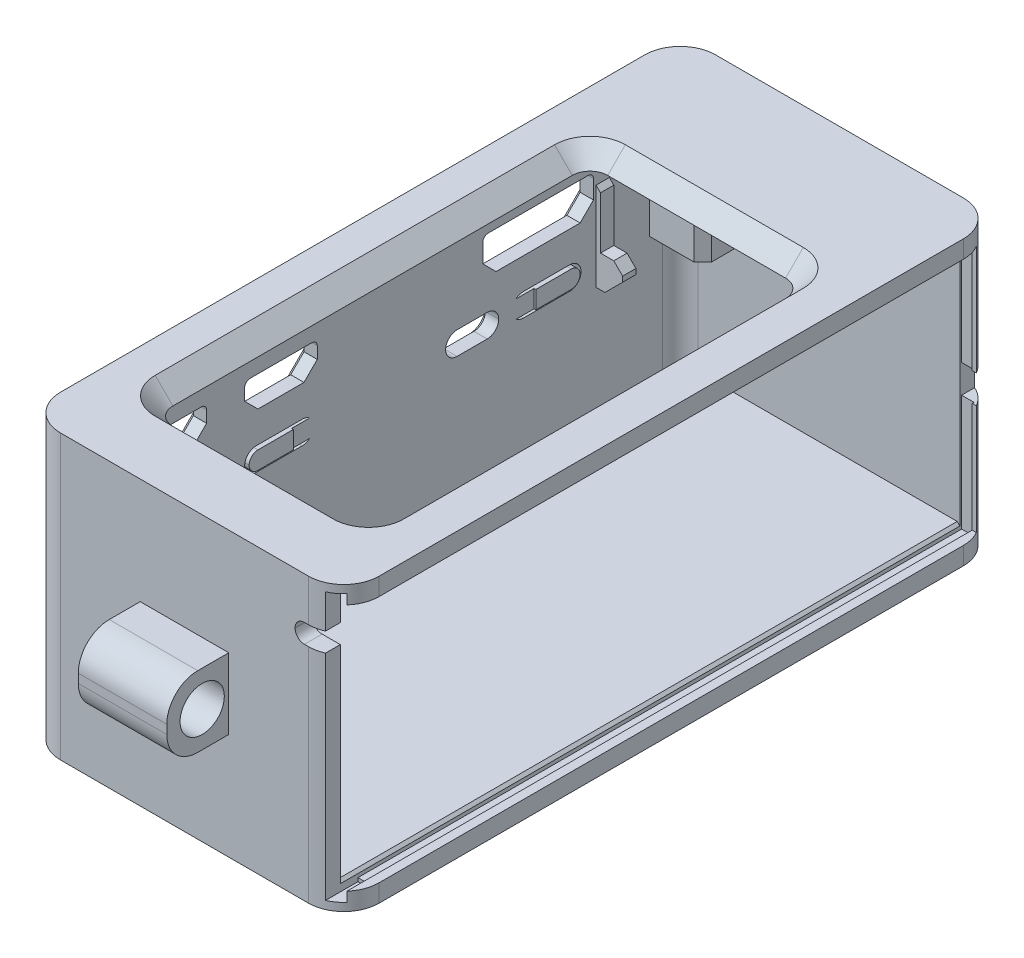
SolidWorks part; units mm, degrees
ref_plane "前视基准面" through (0, 0, 0) normal (0, 0, 1) x (1, 0, 0)
ref_plane "上视基准面" through (0, 0, 0) normal (0, 1, 0) x (1, 0, 0)
ref_plane "右视基准面" through (0, 0, 0) normal (1, 0, 0) x (0, 0, -1)
sketch "草图1" plane through (0, 0, 0) normal (1, 0, 0) x (0, 0, -1)
  line L1 (-54.0501, 29.0398) -> (19.9499, 29.0398)
  line L2 (-54.0501, 29.0398) -> (-54.0501, -2.9602)
  line L3 (-54.0501, -2.9602) -> (19.9499, -2.9602)
  line L4 (19.9499, 29.0398) -> (19.9499, -2.9602)
  dimension "D1" = 74
  dimension "D2" = 32
extrude "凸台-拉伸1" add sketch "草图1" along normal blind 36
sketch "草图2" plane through (36, 0, 0) normal (1, 0, 0) x (0, 0, -1)
  line L8 (17.9499, -0.9602) -> (17.9499, 27.0398)
  line L9 (-52.0501, -0.9602) -> (17.9499, -0.9602)
  line L10 (-52.0501, 27.0398) -> (-52.0501, -0.9602)
  line L11 (17.9499, 27.0398) -> (-52.0501, 27.0398)
  line L12 (17.9499, -0.9602) -> (17.9499, 27.0398)
  line L13 (-52.0501, -0.9602) -> (17.9499, -0.9602)
  line L14 (-52.0501, 27.0398) -> (-52.0501, -0.9602)
  line L15 (17.9499, 27.0398) -> (-52.0501, 27.0398)
  dimension "D1" = 2
extrude "切除-拉伸1" cut sketch "草图2" against normal blind 34
fillet "圆角1" radius 2 2 edges at (2, 13.0398, -17.9499) (2, 13.0398, 52.0501)
fillet "圆角2" radius 4 4 edges at (0, 13.0398, -19.9499) (0, 13.0398, 54.0501) (36, 13.0398, 54.0501) (36, 13.0398, -19.9499)
sketch "草图3" plane through (0, 29.0398, 0) normal (0, 1, 0) x (1, 0, 0)
  line L0 (32, 19.9499) -> (4, 19.9499) construction
  line L1 (29.8, 4.0599) -> (5.7, 4.0599)
  line L2 (29.8, 4.0599) -> (29.8, -45.0601)
  line L3 (29.8, -45.0601) -> (5.7, -45.0601)
  line L4 (5.7, 4.0599) -> (5.7, -45.0601)
  line L5 (36, 15.9499) -> (36, -50.0501) construction
  line L6 (32, -54.0501) -> (4, -54.0501) construction
  line L7 (0, 15.9499) -> (0, -50.0501) construction
  dimension "D1" = 15.89
  dimension "D2" = 6.2
  dimension "D3" = 8.99
  dimension "D4" = 5.7
extrude "切除-拉伸2" cut sketch "草图3" against normal blind 10
fillet "圆角3" radius 2 4 edges at (5.7, 28.0398, 45.0601) (29.8, 28.0398, 45.0601) (29.8, 28.0398, -4.0599) (5.7, 28.0398, -4.0599)
chamfer "倒角1" distance 2 angle 45 8 edges at (17.75, 29.0398, 45.0601) (29.2142, 29.0398, 44.4744) (6.2858, 29.0398, 44.4744) (29.8, 29.0398, 20.5001) (5.7, 29.0398, 20.5001) (29.2142, 29.0398, -3.4741) (6.2858, 29.0398, -3.4741) (17.75, 29.0398, -4.0599)
sketch "草图4" plane through (0, 0, 0) normal (-1, 0, 0) x (0, 0, 1)
  line L0 (-15.9499, 29.0398) -> (50.0501, 29.0398) construction
  line L1 (-8.1499, 22.4398) -> (4.3501, 22.4398)
  line L2 (-8.1499, 22.4398) -> (-8.1499, 18.2398)
  line L3 (-8.1499, 18.2398) -> (4.3501, 18.2398)
  line L4 (4.3501, 22.4398) -> (4.3501, 18.2398)
  line L5 (23.0501, 21.6812) -> (31.2501, 21.6812)
  line L6 (23.0501, 21.6812) -> (23.0501, 18.2398)
  line L7 (23.0501, 18.2398) -> (31.2501, 18.2398)
  line L8 (31.2501, 21.6812) -> (31.2501, 18.2398)
  line L9 (35.5501, 21.6398) -> (43.7501, 21.6398)
  line L10 (35.5501, 21.6398) -> (35.5501, 18.2398)
  line L11 (35.5501, 18.2398) -> (43.7501, 18.2398)
  line L12 (43.7501, 21.6398) -> (43.7501, 18.2398)
  line L13 (-6.7499, 14.7398) -> (1.0501, 14.7398)
  line L14 (-6.7499, 14.7398) -> (-6.7499, 12.1398)
  line L15 (-6.7499, 12.1398) -> (1.0501, 12.1398)
  line L16 (1.0501, 14.7398) -> (1.0501, 12.1398)
  line L17 (23.4501, 14.7398) -> (31.2501, 14.7398)
  line L18 (23.4501, 14.7398) -> (23.4501, 12.1398)
  line L19 (23.4501, 12.1398) -> (31.2501, 12.1398)
  line L20 (31.2501, 14.7398) -> (31.2501, 12.1398)
  line L21 (33.8696, 14.7398) -> (43.3696, 14.7398)
  line L22 (33.8696, 14.7398) -> (33.8696, 11.5398)
  line L23 (33.8696, 11.5398) -> (43.3696, 11.5398)
  line L24 (43.3696, 14.7398) -> (43.3696, 11.5398)
  line L25 (54.0501, 29.0398) -> (54.0501, -2.9602) construction
  line L27 (8.5501, 14.7398) -> (2.5501, 14.7398)
  line L28 (8.5501, 14.7398) -> (8.5501, 12.1398)
  line L29 (8.5501, 12.1398) -> (2.5501, 12.1398)
  line L30 (2.5501, 14.7398) -> (2.5501, 12.1398)
  dimension "D1" = 14.3
  dimension "D2" = 3.2
  dimension "D3" = 2.6
  dimension "D4" = 7.8
  dimension "D5" = 7.8
  dimension "D6" = 8.2
  dimension "D7" = 8.2
  dimension "D8" = 3.4
  dimension "D9" = 12.5
  dimension "D10" = 4.2
  dimension "D11" = 10.8
  dimension "D12" = 10.3
  dimension "D13" = 4.3
  dimension "D14" = 18.7
  dimension "D15" = 9.5
  dimension "D16" = 53
  dimension "D17" = 1.5
  dimension "D18" = 6
extrude "切除-拉伸3" cut sketch "草图4" against normal blind 10
fillet "圆角8" radius 1.3 4 edges at (1, 14.7398, 2.5501) (1, 14.7398, 8.5501) (1, 12.1398, 8.5501) (1, 12.1398, 2.5501)
sketch "草图5" plane through (2, 0, 0) normal (1, 0, 0) x (0, 0, -1)
  line L0 (-23.4501, 12.1398) -> (-23.4501, 14.7398) construction
  line L1 (-23.4501, 14.4398) -> (-30.9501, 14.4398)
  line L2 (-23.4501, 14.4398) -> (-23.4501, 12.4398)
  line L3 (-23.4501, 12.4398) -> (-30.9501, 12.4398)
  line L4 (-30.9501, 14.4398) -> (-30.9501, 12.4398)
  line L5 (-1.0501, 14.7398) -> (-1.0501, 12.1398) construction
  line L6 (-1.0501, 12.4398) -> (6.4499, 12.4398)
  line L7 (-1.0501, 12.4398) -> (-1.0501, 14.4398)
  line L8 (-1.0501, 14.4398) -> (6.4499, 14.4398)
  line L9 (6.4499, 12.4398) -> (6.4499, 14.4398)
  line L10 (-23.4501, 14.7398) -> (-31.2501, 14.7398) construction
  line L11 (-31.2501, 12.1398) -> (-23.4501, 12.1398) construction
  line L12 (-31.2501, 14.7398) -> (-31.2501, 12.1398) construction
  line L13 (6.7499, 14.7398) -> (-1.0501, 14.7398) construction
  line L14 (-1.0501, 12.1398) -> (6.7499, 12.1398) construction
  line L15 (6.7499, 12.1398) -> (6.7499, 14.7398) construction
  dimension "D1" = 0.3
  dimension "D2" = 0.3
  dimension "D3" = 0.3
  dimension "D4" = 0.3
  dimension "D5" = 0.3
  dimension "D6" = 0.3
extrude "凸台-拉伸2" add sketch "草图5" against normal blind 1.2
sketch "草图6" plane through (0.8, 0, 0) normal (-1, 0, 0) x (0, 0, 1)
  line L0 (1.0501, 12.4398) -> (-6.4499, 12.4398) construction
  line L1 (-6.4499, 14.4398) -> (-1.4499, 14.4398)
  line L2 (-6.4499, 14.4398) -> (-6.4499, 12.4398)
  line L3 (-6.4499, 12.4398) -> (-1.4499, 12.4398)
  line L4 (-1.4499, 14.4398) -> (-1.4499, 12.4398)
  line L5 (30.9501, 12.4398) -> (23.4501, 12.4398) construction
  line L6 (30.9501, 14.4398) -> (25.9501, 14.4398)
  line L7 (30.9501, 14.4398) -> (30.9501, 12.4398)
  line L8 (30.9501, 12.4398) -> (25.9501, 12.4398)
  line L9 (25.9501, 14.4398) -> (25.9501, 12.4398)
  dimension "D1" = 5
  dimension "D2" = 5
extrude "凸台-拉伸3" add sketch "草图6" along normal blind 1.5 and the other way blind 1.4
fillet "圆角4" radius 0.6 10 edges at (1, 11.5398, 33.8696) (1, 14.7398, 33.8696) (1, 14.7398, 43.3696) (1, 11.5398, 43.3696) (1, 21.6398, 35.5501) (1, 21.6398, 43.7501) (1, 21.6812, 31.2501) (1, 21.6812, 23.0501) (1, 22.4398, -8.1499) (1, 22.4398, 4.3501)
chamfer "倒角2" distance 1.5 angle 45 6 edges at (1, 18.2398, 43.7501) (1, 18.2398, 35.5501) (1, 18.2398, 31.2501) (1, 18.2398, 23.0501) (1, 18.2398, 4.3501) (1, 18.2398, -8.1499)
fillet "圆角5" radius 1 8 edges at (0.05, 12.4398, 25.9501) (0.05, 14.4398, 25.9501) (0.75, 12.4398, 30.9501) (0.75, 14.4398, 30.9501) (0.05, 12.4398, -1.4499) (0.05, 14.4398, -1.4499) (0.75, 12.4398, -6.4499) (0.75, 14.4398, -6.4499)
chamfer "倒角10" distance 0.2 angle 45 12 edges at (-0.7, 12.4398, 28.4501) (-0.7, 12.7327, 30.6572) (-0.7, 12.7327, 26.243) (-0.7, 14.1469, 30.6572) (-0.7, 14.1469, 26.243) (-0.7, 14.4398, 28.4501) (-0.7, 12.4398, -3.9499) (-0.7, 12.7327, -1.7428) (-0.7, 12.7327, -6.157) (-0.7, 14.1469, -1.7428) (-0.7, 14.1469, -6.157) (-0.7, 14.4398, -3.9499)
fillet "圆角6" radius 1.3 8 edges at (1, 14.7398, 1.0501) (1, 12.1398, 1.0501) (1, 12.1398, -6.7499) (1, 14.7398, -6.7499) (1, 14.7398, 23.4501) (1, 12.1398, 23.4501) (1, 12.1398, 31.2501) (1, 14.7398, 31.2501)
chamfer "倒角4" distance 0.5 angle 45 50 edges at (0, 12.1398, -2.8499) (0, 12.5206, 0.6694) (0, 12.5206, -6.3691) (0, 14.359, 0.6694) (0, 14.359, -6.3691) (0, 14.7398, -2.8499) (0, 18.9898, -7.3999) (0, 18.2398, -1.8999) (0, 18.9898, 3.6001) (0, 20.7898, 4.3501) (0, 20.7898, -8.1499) (0, 22.2641, 4.1744) (0, 22.2641, -7.9741) (0, 22.4398, -1.8999) (0, 11.5398, 38.6196) (0, 11.7155, 43.1938) (0, 11.7155, 34.0453) (0, 13.1398, 43.3696) (0, 13.1398, 33.8696) (0, 14.5641, 43.1938) (0, 14.5641, 34.0453) (0, 14.7398, 38.6196) (0, 12.1398, 27.3501) (0, 12.5206, 30.8694) (0, 12.5206, 23.8309) (0, 14.359, 30.8694) (0, 14.359, 23.8309) (0, 14.7398, 27.3501) (0, 20.4105, 23.0501) (0, 21.5055, 23.2259) (0, 21.6812, 27.1501) (0, 21.5055, 31.0744) (0, 18.9898, 23.8001) (0, 18.2398, 27.1501) (0, 18.9898, 30.5001) (0, 20.4105, 31.2501) (0, 18.9898, 43.0001) (0, 18.2398, 39.6501) (0, 18.9898, 36.3001) (0, 20.3898, 35.5501) (0, 21.4641, 35.7259) (0, 21.6398, 39.6501) (0, 20.3898, 43.7501) (0, 21.4641, 43.5744) (0, 12.5206, 8.1694) (0, 12.1398, 5.5501) (0, 12.5206, 2.9309) (0, 14.359, 8.1694) (0, 14.7398, 5.5501) (0, 14.359, 2.9309)
sketch "草图7" plane through (2, 0, 0) normal (1, 0, 0) x (0, 0, -1)
  line L0 (15.9499, 27.0398) -> (-50.0501, 27.0398) construction
  line L1 (-46.0501, 21.0398) -> (-44.5501, 21.0398)
  line L2 (-46.0501, 21.0398) -> (-46.0501, 11.0398)
  line L3 (-46.0501, 11.0398) -> (-44.5501, 11.0398)
  line L4 (-44.5501, 21.0398) -> (-44.5501, 11.0398)
  line L5 (8.4499, 21.0398) -> (9.9499, 21.0398)
  line L6 (8.4499, 21.0398) -> (8.4499, 11.0398)
  line L7 (8.4499, 11.0398) -> (9.9499, 11.0398)
  line L8 (9.9499, 21.0398) -> (9.9499, 11.0398)
  line L11 (17.9499, -0.9602) -> (17.9499, 27.0398) construction
  line L12 (-52.0501, 27.0398) -> (-52.0501, -0.9602) construction
  dimension "D1" = 6
  dimension "D2" = 10
  dimension "D3" = 1.5
  dimension "D4" = 1.5
  dimension "D5" = 8
  dimension "D6" = 6
extrude "凸台-拉伸4" add sketch "草图7" along normal blind 0.5
sketch "草图10" plane through (2.5, 0, 0) normal (1, 0, 0) x (0, 0, -1)
  line L1 (-46.0501, 11.0398) -> (-44.5501, 11.0398)
  line L2 (-46.0501, 11.0398) -> (-46.0501, 14.6398)
  line L3 (-46.0501, 14.6398) -> (-44.5501, 14.6398)
  line L4 (-44.5501, 11.0398) -> (-44.5501, 14.6398)
  line L7 (8.4499, 11.0398) -> (9.9499, 11.0398)
  line L8 (8.4499, 11.0398) -> (8.4499, 14.6398)
  line L9 (8.4499, 14.6398) -> (9.9499, 14.6398)
  line L10 (9.9499, 11.0398) -> (9.9499, 14.6398)
  dimension "D1" = 3.6
extrude "凸台-拉伸6" add sketch "草图10" along normal blind 2.5
chamfer "倒角7" distance 1 angle 45 2 edges at (5, 14.6398, -9.1999) (5, 14.6398, 45.3001)
chamfer "倒角8" distance 2 angle 45 2 edges at (5, 11.0398, 45.3001) (5, 11.0398, -9.1999)
chamfer "倒角5" distance 0.5 angle 45 2 edges at (2.5, 21.0398, 45.3001) (2.5, 21.0398, -9.1999)
sketch "草图8" plane through (2, 0, 0) normal (1, 0, 0) x (0, 0, -1)
  line L1 (-52.0501, 22.2398) -> (-48.0501, 22.2398)
  line L2 (-52.0501, 22.2398) -> (-52.0501, 24.2398)
  line L3 (-52.0501, 24.2398) -> (-48.0501, 24.2398)
  line L4 (-48.0501, 22.2398) -> (-48.0501, 24.2398)
  line L6 (17.9499, 24.2398) -> (11.9499, 24.2398)
  line L7 (17.9499, 24.2398) -> (17.9499, 22.2398)
  line L8 (17.9499, 22.2398) -> (11.9499, 22.2398)
  line L9 (11.9499, 24.2398) -> (11.9499, 22.2398)
  line L10 (15.9499, 27.0398) -> (-50.0501, 27.0398) construction
  line L11 (17.9499, -0.9602) -> (17.9499, 27.0398) construction
  line L12 (-52.0501, 27.0398) -> (-52.0501, -0.9602) construction
  dimension "D1" = 2.8
  dimension "D2" = 2
  dimension "D3" = 4
  dimension "D4" = 6
extrude "凸台-拉伸5" add sketch "草图8" along normal blind 5
chamfer "倒角6" distance 1 angle 45 2 edges at (7, 24.2398, -14.9499) (7, 24.2398, 50.0501)
sketch "草图12" plane through (0, 0, 54.0501) normal (0, 0, 1) x (1, 0, 0)
  line L0 (4, -0.9602) -> (35.4641, -0.9602) construction
  line L1 (36, 27.0398) -> (33.6, 27.0398)
  line L2 (36, 27.0398) -> (36, -0.9602)
  line L3 (36, -0.9602) -> (33.6, -0.9602)
  line L4 (33.6, 27.0398) -> (33.6, -0.9602)
  dimension "D1" = 2.4
extrude "切除-拉伸5" cut sketch "草图12" against normal blind 10.8
sketch "草图11" plane through (0, -0.9602, 0) normal (0, 1, 0) x (1, 0, 0)
  line L0 (32, 19.9499) -> (4, 19.9499) construction
  line L1 (35, 17.9499) -> (33.6, 17.9499)
  line L2 (35, 17.9499) -> (35, -54.0501)
  line L3 (35, -54.0501) -> (33.6, -54.0501)
  line L4 (33.6, 17.9499) -> (33.6, -54.0501)
  line L5 (32, -54.0501) -> (4, -54.0501) construction
  line L6 (36, -50.0501) -> (36, 15.9499) construction
  dimension "D1" = 2
  dimension "D2" = 0
  dimension "D3" = 1
  dimension "D4" = 1.4
extrude "切除-拉伸4" cut sketch "草图11" against normal blind 0.7
sketch "草图13" plane through (0, 27.0398, 0) normal (0, -1, 0) x (1, 0, 0)
  line L10 (33.6, -17.9499) -> (35, -17.9499)
  line L11 (33.6, 54.0501) -> (33.6, -17.9499)
  line L12 (35, 54.0501) -> (33.6, 54.0501)
  line L13 (35, -17.9499) -> (35, 54.0501)
  line L14 (33.6, -17.9499) -> (35, -17.9499)
  line L15 (33.6, 54.0501) -> (33.6, -17.9499)
  line L16 (35, 54.0501) -> (33.6, 54.0501)
  line L17 (35, -17.9499) -> (35, 54.0501)
  dimension "D1" = 0
extrude "切除-拉伸6" cut sketch "草图13" against normal blind 0.7
sketch "草图14" plane through (0, -1.6602, 0) normal (0, 1, 0) x (1, 0, 0)
  line L1 (33.6, -54.0501) -> (35, -54.0501)
  line L2 (33.6, -54.0501) -> (33.6, -50.0501)
  line L3 (33.6, -50.0501) -> (35, -50.0501)
  line L4 (35, -54.0501) -> (35, -50.0501)
  line L5 (32, -54.0501) -> (4, -54.0501) construction
  line L6 (33.6, -53.7162) -> (33.6, 17.9499) construction
  dimension "D1" = 4
extrude "切除-拉伸7" cut sketch "草图14" against normal blind 0.4
sketch "草图15" plane through (0, 27.7398, 0) normal (0, -1, 0) x (1, 0, 0)
  line L3 (35, 50.0501) -> (35, 52.6959)
  line L4 (33.6, 50.0501) -> (35, 50.0501)
  line L5 (33.6, 53.7162) -> (33.6, 50.0501)
  line L7 (33.6, 50.0501) -> (35, 50.0501)
  line L8 (33.6, 53.7162) -> (33.6, 50.0501)
  line L10 (35, 50.0501) -> (35, 52.6959)
  arc A1 (35, 52.6959) -> (33.6, 53.7162) centre (32, 50.0501) ccw
  arc A2 (35, 52.6959) -> (33.6, 53.7162) centre (32, 50.0501) ccw
  dimension "D1" = 0
extrude "切除-拉伸8" cut sketch "草图15" against normal blind 0.4
sketch "草图16" plane through (0, 0, -17.9499) normal (0, 0, 1) x (1, 0, 0)
  line L0 (33.6, 28.1398) -> (33.6, -2.0602) construction
  line L1 (33.6, 27.7398) -> (35, 27.7398)
  line L2 (33.6, 27.7398) -> (33.6, -1.6602)
  line L3 (33.6, -1.6602) -> (35, -1.6602)
  line L4 (35, 27.7398) -> (35, -1.6602)
extrude "切除-拉伸9" cut sketch "草图16" against normal blind 0.2
chamfer "倒角9" distance 0.3 angle 45 2 edges at (33.6, 27.0398, 17.0501) (33.6, -0.9602, 17.0501)
ref_plane "基准面4" through (0, 13.0398, 0) normal (0, -1, 0) x (-1, 0, 0)
sketch "草图19" plane through (0, 0, -18.1499) normal (0, 0, 1) x (1, 0, 0)
  line L0 (35, 13.0398) -> (40.512, 13.0398) construction
  line L1 (35.4641, -0.9602) -> (35.4641, 27.0398) construction
  line L3 (34.3, 27.7398) -> (34.3, 24.7272) construction
  line L4 (33.6, 27.7398) -> (35, 27.7398) construction
  line L6 (33.6, 14.6398) -> (35.4641, 14.6398)
  line L7 (33.6, 14.6398) -> (33.6, 11.4398)
  line L8 (33.6, 11.4398) -> (35.4641, 11.4398)
  line L9 (35.4641, 14.6398) -> (35.4641, 11.4398)
  line L10 (33.6, 14.6398) -> (35.4641, 11.4398) construction
  line L11 (33.6, 11.4398) -> (35.4641, 14.6398) construction
  point P2 (34.3, 13.0398)
  point P10 (34.5321, 13.0398)
  point P13 (35.4641, 13.0398)
  point P16 (34.3, 27.7398)
  dimension "D1" = 3.2
extrude "切除-拉伸11" cut sketch "草图19" against normal blind 10 and the other way blind 2
sketch "草图20" plane through (0, 0, 54.0501) normal (0, 0, 1) x (1, 0, 0)
  line L0 (33.6, 24.2398) -> (33.6, 28.1198) construction
  line L1 (33.6, 24.2898) -> (30.5, 24.2898)
  line L2 (33.6, 24.2898) -> (33.6, 22.1398)
  line L3 (33.6, 22.1398) -> (30.5, 22.1398)
  line L4 (30.5, 24.2898) -> (30.5, 22.1398)
  line L5 (32, 29.0398) -> (4, 29.0398) construction
  dimension "D1" = 4.75
  dimension "D2" = 2.15
  dimension "D3" = 3.1
extrude "切除-拉伸12" cut sketch "草图20" against normal up to next
fillet "圆角9" radius 1.05 2 edges at (30.5, 24.2898, 53.0501) (30.5, 22.1398, 53.0501)
sketch "草图21" plane through (0, 0, -19.9499) normal (0, 0, -1) x (-1, 0, 0)
  line L0 (-25, 19.5398) -> (-14, 19.5398) construction
  line L1 (-25, 21.0398) -> (-14, 21.0398)
  line L2 (-25, 18.0398) -> (-14, 18.0398)
  line L3 (-4, -2.9602) -> (-4, 29.0398) construction
  line L4 (-32, 29.0398) -> (-4, 29.0398) construction
  arc A0 (-25, 21.0398) -> (-25, 18.0398) centre (-25, 19.5398) ccw
  arc A1 (-14, 18.0398) -> (-14, 21.0398) centre (-14, 19.5398) ccw
  point P2 (-19.5, 19.5398)
  dimension "D4" = 1.5
  dimension "D1" = 10
  dimension "D2" = 9.5
  dimension "D3" = 11
extrude "切除-拉伸13" cut sketch "草图21" against normal up to next
sketch "草图22" plane through (0, -2.9602, 0) normal (0, -1, 0) x (1, 0, 0)
  line L0 (7.7, -6.0599) -> (27.8, -6.0599) construction
  line B0 (13.068, 7.4573) -> (12.595, 6.6368)
  line B1 (12.595, 6.6368) -> (10.1389, 2.3799)
  line B2 (10.1389, 2.3799) -> (9.6602, 1.5593)
  line B3 (9.6602, -0.1617) -> (10.1389, -0.9823)
  line B4 (10.1389, -0.9823) -> (12.595, -5.2392)
  line B5 (12.595, -5.2392) -> (13.068, -6.0599)
  line B6 (14.5553, -6.9204) -> (21.3709, -6.9204)
  line B7 (22.8583, -6.0599) -> (23.3313, -5.2392)
  line B8 (23.3313, -5.2392) -> (25.7874, -0.9823)
  line B9 (25.7874, -0.9823) -> (26.2661, -0.1617)
  line B10 (26.2661, 1.5593) -> (25.7874, 2.3799)
  line B11 (25.7874, 2.3799) -> (23.3313, 6.6368)
  line B12 (23.3313, 6.6368) -> (22.8583, 7.4573)
  line B13 (21.3709, 8.3178) -> (14.5553, 8.3178)
  line B14 (13.7461, -4.9657) -> (10.703, 0.2999)
  line B15 (10.703, 1.1034) -> (13.7518, 6.3404)
  line B16 (14.4528, 6.3461) -> (17.4958, 1.2573)
  line B17 (22.6531, 2.8358) -> (22.9836, 2.2431)
  line B18 (23.0805, 2.1861) -> (24.7901, 2.1861)
  line B19 (24.887, 2.1292) -> (25.5138, 1.0236)
  line B20 (25.417, 0.8583) -> (20.14, 0.8583)
  line B21 (20.0431, 0.9153) -> (18.9775, 2.7959)
  line B22 (22.2998, 6.7393) -> (22.921, 5.6452)
  line B23 (22.8241, 5.4799) -> (20.311, 5.4799)
  line B24 (20.2141, 5.537) -> (19.5986, 6.6311)
  line B25 (19.6955, 6.7963) -> (22.2029, 6.7963)
  line B26 (21.6388, 2.7674) -> (21.9009, 2.2431)
  line B27 (21.7812, 2.1861) -> (20.4364, 2.1861)
  line B28 (20.3395, 2.2431) -> (20.0659, 2.7332)
  line B29 (15.034, 12.3126) -> (15.034, 10.4377)
  line B30 (15.034, 10.4377) -> (21.5989, 10.4377)
  line B31 (21.5989, 10.4377) -> (21.5989, 11.2698)
  line B32 (21.5989, 11.2698) -> (18.9946, 11.2698)
  line B33 (18.9946, 11.2698) -> (18.9946, 12.3582)
  line B34 (18.3221, 12.25) -> (18.3221, 11.2698)
  line B35 (18.3221, 11.2698) -> (15.7065, 11.2698)
  line B36 (15.7065, 11.2698) -> (15.7065, 12.2158)
  line B37 (16.7322, 15.8514) -> (21.5989, 15.8514)
  line B38 (21.5989, 15.8514) -> (21.5989, 16.6665)
  line B39 (21.5989, 16.6665) -> (16.7322, 16.6665)
  line B40 (16.7322, 16.6665) -> (16.7322, 15.8514)
  line B41 (17.8093, 21.3735) -> (17.4787, 20.5415)
  line B42 (16.6923, 21.6983) -> (15.6894, 22.4962)
  line B43 (18.6527, 19.265) -> (19.0117, 20.1141)
  line B44 (19.6613, 18.564) -> (20.7669, 17.658)
  line B45 (16.5043, 26.4795) -> (19.8437, 26.4795)
  line B46 (19.4562, 25.0377) -> (16.5043, 25.0377)
  line B47 (16.5043, 25.0377) -> (16.5043, 23.4478)
  line B48 (16.5043, 23.4478) -> (19.6556, 23.4478)
  line B49 (20.8979, 26.6277) -> (20.8979, 26.6618)
  line B50 (20.8979, 26.6618) -> (21.5989, 26.7759)
  line B51 (21.5989, 26.7759) -> (21.5989, 28.0751)
  line B52 (21.5989, 28.0751) -> (16.5043, 28.0751)
  line B53 (16.5043, 28.0751) -> (16.5043, 26.4795)
  line B54 (20.5959, 31.9274) -> (20.5959, 31.1239)
  line B55 (17.6554, 33.0216) -> (17.6554, 33.8079)
  line B56 (17.6554, 33.8079) -> (16.5043, 33.8079)
  line B57 (16.5043, 33.8079) -> (16.5043, 31.9388)
  line B58 (19.5474, 29.6878) -> (19.5816, 29.6878)
  line B59 (21.4108, 29.591) -> (21.4564, 29.591)
  line B60 (21.8154, 31.141) -> (21.8154, 31.6254)
  line B61 (17.0456, 34.2638) -> (18.0942, 34.8223)
  line B62 (21.086, 37.0676) -> (21.086, 37.1075)
  line B63 (21.086, 37.1075) -> (21.5989, 37.2214)
  line B64 (21.5989, 37.2214) -> (21.5989, 38.5207)
  line B65 (21.5989, 38.5207) -> (18.704, 38.5207)
  line B66 (19.2681, 36.9251) -> (20.083, 36.9251)
  line B67 (17.3876, 41.0111) -> (17.3876, 40.9769)
  line B68 (17.3876, 40.9769) -> (16.5043, 40.8686)
  line B69 (16.5043, 40.8686) -> (16.5043, 39.5693)
  line B70 (16.5043, 39.5693) -> (21.5989, 39.5693)
  line B71 (21.5989, 39.5693) -> (21.5989, 41.1536)
  line B72 (21.5989, 41.1536) -> (18.6869, 41.1536)
  line B73 (17.8548, 42.8118) -> (16.4815, 43.0796)
  line B74 (21.9009, 2.2431) -> (22.9836, 2.2431)
  line B75 (21.7812, 2.1861) -> (23.0805, 2.1861)
  spline B76 degree 3 poles (9.6602, 1.5593) (9.512, 1.2914) (9.4322, 0.9951) (9.4322, 0.6988) knots 3 3 3 3 4 4 4 4
  spline B77 degree 3 poles (9.4322, 0.6988) (9.4322, 0.4025) (9.512, 0.1061) (9.6602, -0.1617) knots 4 4 4 4 5 5 5 5
  spline B78 degree 3 poles (13.068, -6.0599) (13.3757, -6.5898) (13.9456, -6.9204) (14.5553, -6.9204) knots 8 8 8 8 9 9 9 9
  spline B79 degree 3 poles (21.3709, -6.9204) (21.9864, -6.9204) (22.5506, -6.5898) (22.8583, -6.0599) knots 10 10 10 10 11 11 11 11
  spline B80 degree 3 poles (26.2661, -0.1617) (26.4199, 0.1061) (26.494, 0.4025) (26.494, 0.6988) knots 14 14 14 14 15 15 15 15
  spline B81 degree 3 poles (26.494, 0.6988) (26.494, 0.9951) (26.4199, 1.2914) (26.2661, 1.5593) knots 15 15 15 15 16 16 16 16
  spline B82 degree 3 poles (22.8583, 7.4573) (22.5506, 7.993) (21.9864, 8.3178) (21.3709, 8.3178) knots 19 19 19 19 20 20 20 20
  spline B83 degree 3 poles (14.5553, 8.3178) (13.9456, 8.3178) (13.3757, 7.993) (13.068, 7.4573) knots 21 21 21 21 22 22 22 22
  spline B84 degree 2 poles (17.4958, 0.146) (14.5211, -5.0056) (14.5154, -5.017) knots 0 0 0 1 1 1
  spline B85 degree 3 poles (14.5154, -5.017) (14.3217, -5.2848) (13.9114, -5.2563) (13.7461, -4.9657) knots 1 1 1 1 2 2 2 2
  spline B86 degree 3 poles (10.703, 0.2999) (10.5606, 0.5449) (10.5606, 0.8527) (10.703, 1.1034) knots 3 3 3 3 4 4 4 4
  spline B87 degree 3 poles (13.7518, 6.3404) (13.9057, 6.6082) (14.2932, 6.6139) (14.4528, 6.3461) knots 5 5 5 5 6 6 6 6
  spline B88 degree 3 poles (17.4958, 1.2573) (17.6953, 0.9153) (17.6953, 0.4879) (17.4958, 0.146) knots 7 7 7 7 8 8 8 8
  spline B89 degree 3 poles (24.7901, 2.1861) (24.83, 2.1861) (24.8642, 2.169) (24.887, 2.1292) knots 3 3 3 3 4 4 4 4
  spline B90 degree 3 poles (25.5138, 1.0236) (25.5537, 0.9495) (25.5025, 0.8583) (25.417, 0.8583) knots 5 5 5 5 6 6 6 6
  spline B91 degree 3 poles (20.14, 0.8583) (20.1001, 0.8583) (20.0602, 0.8754) (20.0431, 0.9153) knots 7 7 7 7 8 8 8 8
  spline B92 degree 3 poles (18.9775, 2.7959) (18.2879, 4.0154) (18.1512, 5.024) (19.5189, 5.024) knots 9 9 9 9 10 10 10 10
  spline B93 degree 3 poles (19.5189, 5.024) (20.8353, 5.024) (21.9921, 4.004) (22.6531, 2.8358) knots 10 10 10 10 11 11 11 11
  spline B94 degree 3 poles (22.2029, 6.7963) (22.2428, 6.7963) (22.2827, 6.7735) (22.2998, 6.7393) knots 0 0 0 0 1 1 1 1
  spline B95 degree 3 poles (22.921, 5.6452) (22.9609, 5.5711) (22.9095, 5.4799) (22.8241, 5.4799) knots 2 2 2 2 3 3 3 3
  spline B96 degree 3 poles (20.311, 5.4799) (20.2711, 5.4799) (20.2369, 5.5027) (20.2141, 5.537) knots 4 4 4 4 5 5 5 5
  spline B97 degree 3 poles (19.5986, 6.6311) (19.5588, 6.7051) (19.61, 6.7963) (19.6955, 6.7963) knots 6 6 6 6 7 7 7 7
  spline B98 degree 3 poles (17.9289, 6.141) (17.6782, 6.5798) (17.7865, 6.8932) (18.1854, 6.8932) (18.5786, 6.8932) (19.0402, 6.5798) (19.2852, 6.141) knots 2 2 2 2 3 3 3 4 4 4 4
  spline B99 degree 3 poles (19.2852, 6.141) (19.5417, 5.6965) (19.4334, 5.3831) (19.0402, 5.3831) (18.6356, 5.3831) (18.1797, 5.6965) (17.9289, 6.141) knots 0 0 0 0 1 1 1 2 2 2 2
  spline B100 degree 3 poles (20.254, 3.7248) (20.7954, 3.7248) (21.274, 3.4171) (21.6388, 2.7674) knots 0 0 0 0 1 1 1 1
  spline B101 degree 3 poles (20.4364, 2.1861) (20.3965, 2.1861) (20.3566, 2.2089) (20.3395, 2.2431) knots 4 4 4 4 5 5 5 5
  spline B102 degree 3 poles (20.0659, 2.7332) (19.7012, 3.3714) (19.6955, 3.7248) (20.254, 3.7248) knots 6 6 6 6 7 7 7 7
  spline B103 degree 3 poles (18.9946, 12.3582) (18.9946, 13.7886) (18.345, 14.7745) (16.9602, 14.7745) knots 5 5 5 5 6 6 6 6
  spline B104 degree 3 poles (16.9602, 14.7745) (15.5241, 14.7745) (15.034, 13.7886) (15.034, 12.3126) knots 6 6 6 6 7 7 7 7
  spline B105 degree 3 poles (15.7065, 12.2158) (15.7065, 13.3669) (16.0085, 13.9482) (16.9602, 13.9482) knots 3 3 3 3 4 4 4 4
  spline B106 degree 3 poles (16.9602, 13.9482) (17.9004, 13.9482) (18.3221, 13.4068) (18.3221, 12.25) knots 4 4 4 4 5 5 5 5
  spline B107 degree 3 poles (15.7293, 16.2618) (15.7293, 16.5866) (15.507, 16.826) (15.205, 16.826) (14.8688, 16.826) (14.675, 16.5866) (14.675, 16.2618) knots 2 2 2 2 3 3 3 4 4 4 4
  spline B108 degree 3 poles (14.675, 16.2618) (14.675, 15.937) (14.8688, 15.6976) (15.205, 15.6976) (15.507, 15.6976) (15.7293, 15.937) (15.7293, 16.2618) knots 0 0 0 0 1 1 1 2 2 2 2
  spline B109 degree 3 poles (17.4787, 20.5415) (17.2451, 19.9545) (17.1026, 19.5328) (16.7322, 19.5328) knots 1 1 1 1 2 2 2 2
  spline B110 degree 3 poles (16.7322, 19.5328) (16.3789, 19.5328) (16.1794, 19.8349) (16.1794, 20.3306) knots 2 2 2 2 3 3 3 3
  spline B111 degree 3 poles (16.1794, 20.3306) (16.1794, 20.8492) (16.3561, 21.2595) (16.6923, 21.6983) knots 3 3 3 3 4 4 4 4
  spline B112 degree 3 poles (15.6894, 22.4962) (15.1024, 21.9149) (14.8061, 21.1) (14.8061, 20.3306) knots 5 5 5 5 6 6 6 6
  spline B113 degree 3 poles (14.8061, 20.3306) (14.8061, 18.9117) (15.7065, 17.9087) (16.8234, 17.9087) knots 6 6 6 6 7 7 7 7
  spline B114 degree 3 poles (16.8234, 17.9087) (17.7922, 17.9087) (18.3734, 18.564) (18.6527, 19.265) knots 7 7 7 7 8 8 8 8
  spline B115 degree 3 poles (19.0117, 20.1141) (19.251, 20.684) (19.3764, 21.0544) (19.7639, 21.0544) knots 9 9 9 9 10 10 10 10
  spline B116 degree 3 poles (19.7639, 21.0544) (20.1229, 21.0544) (20.3452, 20.7752) (20.3452, 20.1825) knots 10 10 10 10 11 11 11 11
  spline B117 degree 3 poles (20.3452, 20.1825) (20.3452, 19.6582) (20.0659, 19.037) (19.6613, 18.564) knots 11 11 11 11 12 12 12 12
  spline B118 degree 3 poles (20.7669, 17.658) (21.3994, 18.3475) (21.7243, 19.282) (21.7243, 20.1483) knots 13 13 13 13 14 14 14 14
  spline B119 degree 3 poles (21.7243, 20.1483) (21.7243, 21.761) (20.7498, 22.6955) (19.6385, 22.6955) knots 14 14 14 14 15 15 15 15
  spline B120 degree 3 poles (19.6385, 22.6955) (18.6983, 22.6955) (18.1398, 22.1998) (17.8093, 21.3735) knots 15 15 15 15 16 16 16 16
  spline B121 degree 3 poles (19.8437, 26.4795) (20.2198, 26.2117) (20.3623, 25.9894) (20.3623, 25.6304) knots 1 1 1 1 2 2 2 2
  spline B122 degree 3 poles (20.3623, 25.6304) (20.3623, 25.2258) (20.1628, 25.0377) (19.4562, 25.0377) knots 2 2 2 2 3 3 3 3
  spline B123 degree 3 poles (19.6556, 23.4478) (20.9264, 23.4478) (21.7243, 23.9208) (21.7243, 25.032) knots 6 6 6 6 7 7 7 7
  spline B124 degree 3 poles (21.7243, 25.032) (21.7243, 25.7273) (21.3994, 26.206) (20.8979, 26.6277) knots 7 7 7 7 8 8 8 8
  spline B125 degree 3 poles (20.5959, 31.1239) (20.5959, 30.5768) (20.4876, 30.3717) (20.254, 30.3717) knots 1 1 1 1 2 2 2 2
  spline B126 degree 3 poles (20.254, 30.3717) (20.083, 30.3717) (20.0032, 30.4115) (19.895, 30.5312) knots 2 2 2 2 3 3 3 3
  spline B127 degree 3 poles (19.895, 30.5312) (19.9576, 30.7535) (19.9862, 30.9586) (19.9862, 31.1296) knots 3 3 3 3 4 4 4 4
  spline B128 degree 3 poles (19.9862, 31.1296) (19.9862, 32.2579) (19.4676, 33.164) (18.2766, 33.164) knots 4 4 4 4 5 5 5 5
  spline B129 degree 3 poles (18.2766, 33.164) (18.0315, 33.164) (17.7979, 33.1013) (17.6554, 33.0216) knots 5 5 5 5 6 6 6 6
  spline B130 degree 3 poles (16.5043, 31.9388) (16.4188, 31.7051) (16.3789, 31.4259) (16.3789, 31.1296) knots 9 9 9 9 10 10 10 10
  spline B131 degree 3 poles (16.3789, 31.1296) (16.3789, 30.0298) (16.983, 28.9983) (18.231, 28.9983) knots 10 10 10 10 11 11 11 11
  spline B132 degree 3 poles (18.231, 28.9983) (18.8236, 28.9983) (19.2966, 29.3288) (19.5474, 29.6878) knots 11 11 11 11 12 12 12 12
  spline B133 degree 3 poles (19.5816, 29.6878) (19.8152, 29.3573) (20.1742, 29.1236) (20.5332, 29.1236) knots 13 13 13 13 14 14 14 14
  spline B134 degree 3 poles (20.5332, 29.1236) (20.9606, 29.1236) (21.2285, 29.3231) (21.4108, 29.591) knots 14 14 14 14 15 15 15 15
  spline B135 degree 3 poles (21.4564, 29.591) (21.6958, 29.1179) (22.0377, 28.8672) (22.4594, 28.8672) knots 16 16 16 16 17 17 17 17
  spline B136 degree 3 poles (22.4594, 28.8672) (23.3711, 28.8672) (23.7416, 29.8303) (23.7416, 31.0042) knots 17 17 17 17 18 18 18 18
  spline B137 degree 3 poles (23.7416, 31.0042) (23.7416, 32.7765) (22.978, 33.8878) (21.9009, 33.8878) knots 18 18 18 18 19 19 19 19
  spline B138 degree 3 poles (21.9009, 33.8878) (20.9777, 33.8878) (20.5959, 33.1811) (20.5959, 31.9274) knots 19 19 19 19 20 20 20 20
  spline B139 degree 3 poles (19.0288, 31.1296) (19.0288, 30.7649) (18.7609, 30.4857) (18.231, 30.4857) (17.7124, 30.4857) (17.4446, 30.7649) (17.4446, 31.1296) knots 2 2 2 2 3 3 3 4 4 4 4
  spline B140 degree 3 poles (17.4446, 31.1296) (17.4446, 31.5057) (17.7124, 31.7735) (18.231, 31.7735) (18.7609, 31.7735) (19.0288, 31.5057) (19.0288, 31.1296) knots 0 0 0 0 1 1 1 2 2 2 2
  spline B141 degree 3 poles (22.7443, 31.2549) (22.7443, 30.5996) (22.5676, 30.1722) (22.2086, 30.1722) knots 0 0 0 0 1 1 1 1
  spline B142 degree 3 poles (22.2086, 30.1722) (22.0377, 30.1722) (21.8952, 30.252) (21.7527, 30.4115) knots 1 1 1 1 2 2 2 2
  spline B143 degree 3 poles (21.7527, 30.4115) (21.7983, 30.5768) (21.8154, 30.7706) (21.8154, 31.141) knots 2 2 2 2 3 3 3 3
  spline B144 degree 3 poles (21.8154, 31.6254) (21.8154, 32.0983) (21.8781, 32.3662) (22.1801, 32.3662) knots 4 4 4 4 5 5 5 5
  spline B145 degree 3 poles (22.1801, 32.3662) (22.505, 32.3662) (22.7443, 31.9104) (22.7443, 31.2549) knots 5 5 5 5 6 6 6 6
  spline B146 degree 3 poles (16.3789, 36.4579) (16.3789, 35.6657) (16.6467, 34.9363) (17.0456, 34.2638) knots 0 0 0 0 1 1 1 1
  spline B147 degree 3 poles (18.0942, 34.8223) (17.8093, 35.3296) (17.6497, 35.7512) (17.6497, 36.1558) knots 2 2 2 2 3 3 3 3
  spline B148 degree 3 poles (17.6497, 36.1558) (17.6497, 36.6744) (17.889, 36.891) (18.2994, 36.9251) knots 3 3 3 3 4 4 4 4
  spline B149 degree 3 poles (18.2994, 36.9251) (18.5159, 34.9363) (19.0971, 34.0928) (20.1742, 34.0928) knots 4 4 4 4 5 5 5 5
  spline B150 degree 3 poles (20.1742, 34.0928) (21.0233, 34.0928) (21.7243, 34.6684) (21.7243, 35.6088) knots 5 5 5 5 6 6 6 6
  spline B151 degree 3 poles (21.7243, 35.6088) (21.7243, 36.1729) (21.4621, 36.6459) (21.086, 37.0676) knots 6 6 6 6 7 7 7 7
  spline B152 degree 3 poles (18.704, 38.5207) (17.1083, 38.5207) (16.3789, 37.7742) (16.3789, 36.4579) knots 11 11 11 11 12 12 12 12
  spline B153 degree 3 poles (20.083, 36.9251) (20.3338, 36.6915) (20.4876, 36.4806) (20.4876, 36.1558) knots 0 0 0 0 1 1 1 1
  spline B154 degree 3 poles (20.4876, 36.1558) (20.4876, 35.8253) (20.3452, 35.6088) (20.0488, 35.6088) knots 1 1 1 1 2 2 2 2
  spline B155 degree 3 poles (20.0488, 35.6088) (19.6898, 35.6088) (19.4049, 35.9336) (19.2681, 36.9251) knots 2 2 2 2 3 3 3 3
  spline B156 degree 3 poles (16.3789, 42.4642) (16.3789, 41.9513) (16.7094, 41.3872) (17.3876, 41.0111) knots 0 0 0 0 1 1 1 1
  spline B157 degree 3 poles (18.6869, 41.1536) (18.0144, 41.4214) (17.7751, 41.8773) (17.7751, 42.2534) knots 7 7 7 7 8 8 8 8
  spline B158 degree 3 poles (17.7751, 42.2534) (17.7751, 42.4813) (17.8093, 42.6295) (17.8548, 42.8118) knots 8 8 8 8 9 9 9 9
  spline B159 degree 3 poles (16.4815, 43.0796) (16.4188, 42.9372) (16.3789, 42.7663) (16.3789, 42.4642) knots 10 10 10 10 11 11 11 11
sketch_block_instance "块1-1"
sketch_block "块1"
extrude "切除-拉伸14" cut sketch "草图22" against normal blind 0.3
ref_plane "基准面5" through (13, 0, 0) normal (1, 0, 0) x (0, 0, -1)
sketch "草图23" plane through (13, 0, 0) normal (1, 0, 0) x (0, 0, -1)
  line L0 (-54.0501, -2.9602) -> (-54.0501, 22.1398) construction
  line L1 (-54.0501, 17.0398) -> (-61.0501, 17.0398)
  line L2 (-54.0501, 17.0398) -> (-54.0501, 9.0398)
  line L3 (-54.0501, 9.0398) -> (-61.0501, 9.0398)
  line L4 (-61.0501, 17.0398) -> (-61.0501, 9.0398)
  dimension "D1" = 12
  dimension "D2" = 8
  dimension "D3" = 7
extrude "凸台-拉伸7" add sketch "草图23" along normal blind 10
sketch "草图24" plane through (23, 0, 0) normal (1, 0, 0) x (0, 0, -1)
  line L0 (-61.0501, 17.0398) -> (-61.0501, 9.0398) construction
  line L1 (-54.0501, 17.0398) -> (-61.0501, 17.0398) construction
  circle A0 centre (-57.0501, 13.0398) radius 2.5
  dimension "D1" = 5
  dimension "D2" = 4
  dimension "D3" = 4
extrude "切除-拉伸15" cut sketch "草图24" against normal through all
fillet "圆角10" radius 3.5 2 edges at (18, 9.0398, 61.0501) (18, 17.0398, 61.0501)
ref_plane "基准面6" through (0, 15, 0) normal (0, 1, 0) x (1, 0, 0)
sketch "草图25" plane through (0, 15, 0) normal (0, 1, 0) x (1, 0, 0)
  line L0 (8, 14.4999) -> (8, 19.1472)
  line L1 (0, -50.0501) -> (0, 15.9499) construction
  line L2 (0, 15.9499) -> (0, -50.0501) construction
  line L3 (1, 14.4999) -> (1, 17.0058)
  line L4 (32, 19.9499) -> (4, 19.9499) construction
  line L5 (1, 17.0058) -> (3.1414, 19.1472)
  line L7 (8, 14.4999) -> (1, 14.4999)
  line L8 (3.1414, 19.1472) -> (8, 19.1472)
  line L9 (8, -50.5366) -> (1, -50.5366)
  line L11 (1, -50.5366) -> (3.1414, -52.9483)
  line L12 (3.1414, -52.9483) -> (8, -52.9483)
  line L13 (8, -52.9483) -> (8, -50.5366)
  dimension "D1" = 8
  dimension "D2" = 5.45
  dimension "D3" = 1
extrude "凸台-拉伸8" add sketch "草图25" along normal blind 5 and the other way blind 2
chamfer "倒角11" distance 1 angle 45 2 edges at (8, 16.5, 50.5366) (8, 16.5, -14.4999)
